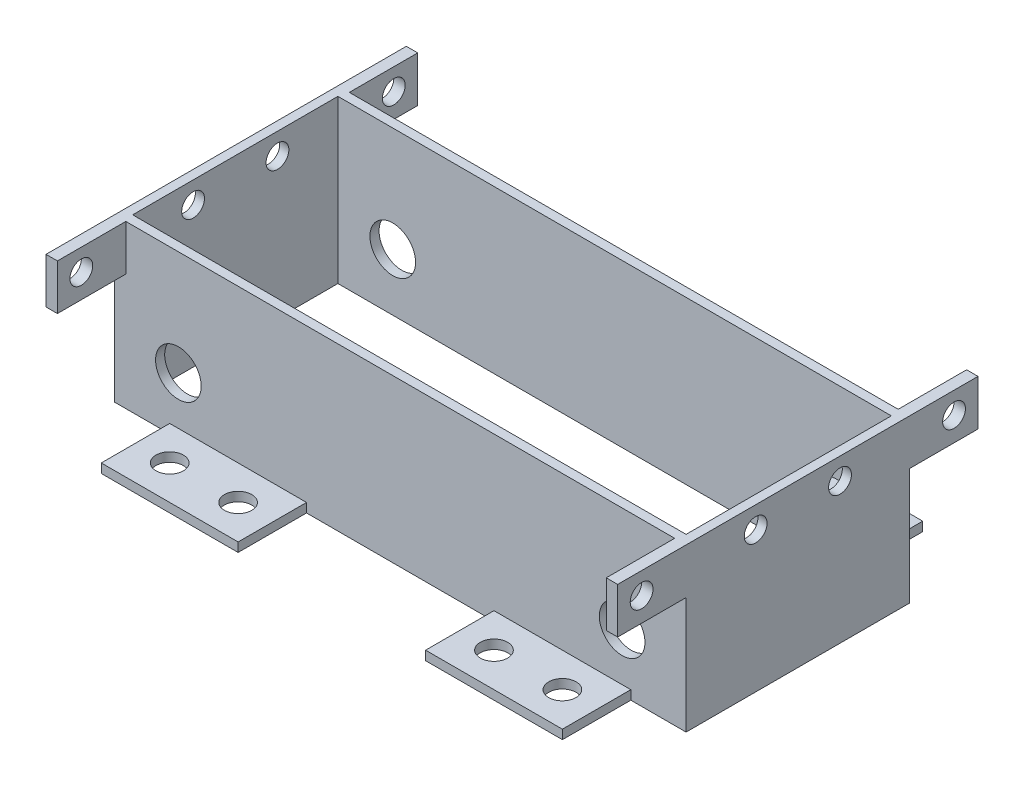
SolidWorks part; units mm, degrees
ref_plane "Front Plane" through (0, 0, 0) normal (0, 0, 1) x (1, 0, 0)
ref_plane "Top Plane" through (0, 0, 0) normal (0, 1, 0) x (1, 0, 0)
ref_plane "Right Plane" through (0, 0, 0) normal (1, 0, 0) x (0, 0, -1)
sketch "Sketch1" plane through (0, 0, 0) normal (0, 0, 1) x (1, 0, 0)
  line L0 (97.29, 0) -> (0, 0) construction
  line L1 (0, 0) -> (97.29, 0) construction
  line L2 (0, 8.025) -> (97.29, 8.025) construction
  line L3 (0, -8.025) -> (97.29, -8.025) construction
  line L4 (105.315, 0) -> (111.315, 0) construction
  line L5 (-14.025, -12.525) -> (111.315, -12.525)
  line L6 (-14.025, -12.525) -> (-14.025, 23.025)
  line L7 (-14.025, 23.025) -> (111.315, 23.025)
  line L9 (97.29, -8.025) -> (97.29, -12.525) construction
  line L10 (97.29, 8.025) -> (97.29, 23.025) construction
  line L11 (111.315, -12.525) -> (111.315, 23.025)
  circle A0 centre (0, 0) radius 8.025 construction
  circle A1 centre (97.29, 0) radius 8.025 construction
  arc A2 (0, 8.025) -> (0, -8.025) centre (0, 0) ccw construction
  arc A3 (97.29, -8.025) -> (97.29, 8.025) centre (97.29, 0) ccw construction
  circle A4 centre (0, 0) radius 5
  circle A5 centre (97.29, 0) radius 5
  point P5 (48.645, 0)
  point P18 (48.645, -12.525)
  dimension "D1" = 16.05
  dimension "D3" = 10
  dimension "D2" = 97.29
  dimension "D4" = 15
  dimension "D5" = 4.5
  dimension "D6" = 6
extrude "Boss-Extrude1" add sketch "Sketch1" along normal blind 2
sketch "Sketch2" plane through (0, 0, 0) normal (0, 0, -1) x (-1, 0, 0)
  line L0 (-111.315, 23.025) -> (14.025, 23.025) construction
  line L1 (-111.315, -12.525) -> (-109.315, -12.525)
  line L2 (-111.315, -12.525) -> (-111.315, 23.025)
  line L3 (-111.315, 23.025) -> (-109.315, 23.025)
  line L4 (-109.315, -12.525) -> (-109.315, 23.025)
  dimension "D1" = 2
extrude "Boss-Extrude2" add sketch "Sketch2" along normal blind 45
ref_plane "Plane1" through (48.645, 0, 0) normal (1, 0, 0) x (0, 0, -1)
mirror "Mirror1" about plane through (48.645, 0, 0) normal (1, 0, 0) of "Boss-Extrude2"
ref_plane "Plane2" through (0, 0, -22.5) normal (0, 0, -1) x (-1, 0, 0)
sketch "Sketch3" plane through (111.315, 0, 0) normal (1, 0, 0) x (0, 0, -1)
  line L0 (0, 23.025) -> (45, 23.025) construction
  line L1 (-2, 23.025) -> (45, 23.025) construction
  line L4 (0, 23.025) -> (13.25, 18.275) construction
  line L5 (22.5, 23.025) -> (22.5, -12.525) construction
  line L6 (-2, -12.525) -> (45, -12.525) construction
  circle A0 centre (13.25, 18.275) radius 2.5
  circle A2 centre (31.75, 18.275) radius 2.5
  circle A3 centre (-11.75, 18.275) radius 2.5
  circle A4 centre (56.75, 18.275) radius 2.5
  dimension "D2" = 5
  dimension "D1" = 4.75
  dimension "D3" = 2
  dimension "D5" = 25
  dimension "D6" = 9.25
  dimension "D4" = 2
sketch "Sketch4" plane through (0, 0, 2) normal (0, 0, 1) x (1, 0, 0)
  line L0 (48.645, 23.025) -> (48.645, -12.525) construction
  line L1 (-1.905, -12.525) -> (28.095, -12.525)
  line L2 (-1.905, -12.525) -> (-1.905, -10.525)
  line L3 (-1.905, -10.525) -> (28.095, -10.525)
  line L4 (28.095, -12.525) -> (28.095, -10.525)
  line L5 (111.315, 23.025) -> (-14.025, 23.025) construction
  line L6 (-14.025, -12.525) -> (111.315, -12.525) construction
  line L7 (13.095, -12.525) -> (48.645, 23.025) construction
  line L8 (99.195, -10.525) -> (69.195, -10.525)
  line L9 (69.195, -12.525) -> (69.195, -10.525)
  line L10 (99.195, -12.525) -> (69.195, -12.525)
  line L11 (99.195, -12.525) -> (99.195, -10.525)
  dimension "D1" = 45
  dimension "D2" = 30
  dimension "D3" = 2
extrude "Boss-Extrude3" add sketch "Sketch4" along normal blind 15
sketch "Sketch5" plane through (0, 0, 2) normal (0, 0, 1) x (1, 0, 0)
  line L0 (48.645, 23.025) -> (48.645, -12.525) construction
  line L1 (-14.025, 23.025) -> (-11.525, 23.025)
  line L2 (-14.025, 23.025) -> (-14.025, 13.025)
  line L3 (-14.025, 13.025) -> (-11.525, 13.025)
  line L4 (-11.525, 23.025) -> (-11.525, 13.025)
  line L5 (111.315, 23.025) -> (-14.025, 23.025) construction
  line L6 (28.095, -12.525) -> (69.195, -12.525) construction
  line L7 (111.315, 13.025) -> (108.815, 13.025)
  line L8 (108.815, 23.025) -> (108.815, 13.025)
  line L9 (111.315, 23.025) -> (108.815, 23.025)
  line L10 (111.315, 23.025) -> (111.315, 13.025)
  dimension "D1" = 2.5
  dimension "D2" = 10
extrude "Boss-Extrude4" add sketch "Sketch5" along normal blind 15
extrude "Cut-Extrude1" cut sketch "Sketch3" against normal through all
sketch "Sketch6" plane through (0, -10.525, 0) normal (0, 1, 0) x (1, 0, 0)
  line L0 (-1.905, -2) -> (13.095, -17) construction
  line L1 (28.095, -17) -> (-1.905, -17) construction
  line L2 (13.095, -17) -> (13.095, -2) construction
  line L3 (28.095, -2) -> (-1.905, -2) construction
  line L4 (48.645, -2) -> (48.645, -17) construction
  line L5 (108.815, -2) -> (-11.525, -2) construction
  line L6 (48.645, -17) -> (28.095, -17) construction
  circle A0 centre (5.595, -9.5) radius 3
  circle A1 centre (20.595, -9.5) radius 3
  circle A2 centre (91.695, -9.5) radius 3
  circle A3 centre (76.695, -9.5) radius 3
  dimension "D1" = 6
extrude "Cut-Extrude2" cut sketch "Sketch6" against normal through all
mirror "Mirror2" about plane through (0, 0, -22.5) normal (0, 0, -1) of "Cut-Extrude2", "Cut-Extrude1", "Boss-Extrude4", "Boss-Extrude3", "Boss-Extrude1"
